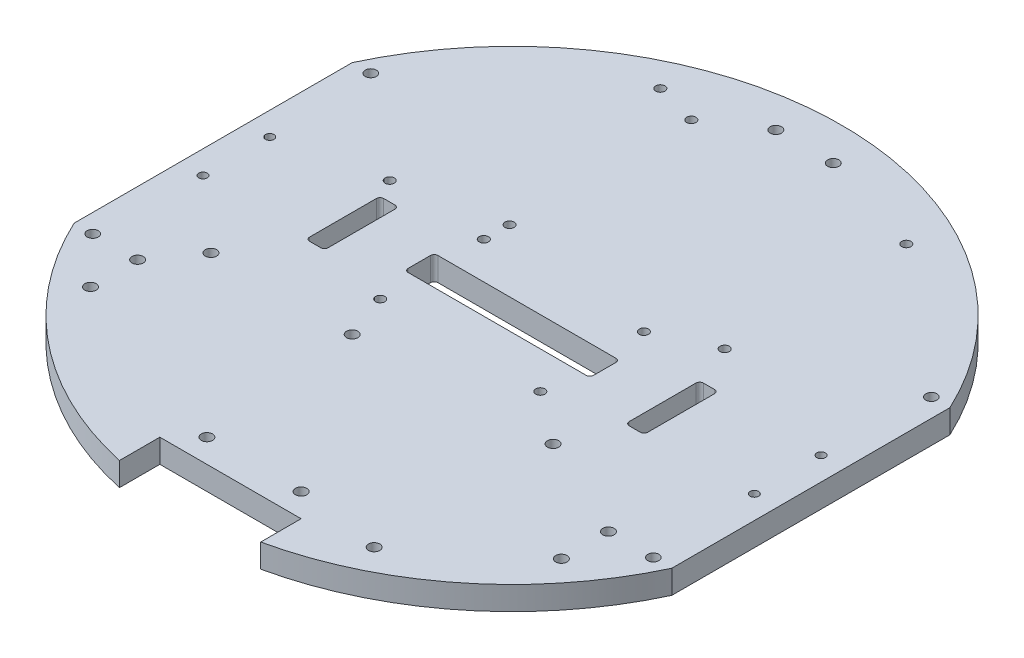
SolidWorks part; units mm, degrees
ref_plane "Front Plane" through (0, 0, 0) normal (0, 0, 1) x (1, 0, 0)
ref_plane "Top Plane" through (0, 0, 0) normal (0, 1, 0) x (1, 0, 0)
ref_plane "Right Plane" through (0, 0, 0) normal (1, 0, 0) x (0, 0, -1)
sketch "Sketch1" plane through (0, 0, 0) normal (0, 1, 0) x (1, 0, 0)
  line L0 (-80.6037, 37.5) -> (-80.6037, -37.5)
  line L1 (0, -88.9) -> (0, 88.9) construction
  line L2 (80.6037, 37.5) -> (80.6037, -37.5)
  arc A0 (-80.6037, -37.5) -> (80.6037, -37.5) centre (0, 0) ccw
  arc A1 (80.6037, 37.5) -> (-80.6037, 37.5) centre (0, 0) ccw
  dimension "D1" = 177.8
  dimension "D2" = 75
extrude "Main Body" add sketch "Sketch1" along normal blind 6.35
sketch "Sketch2" plane through (0, 6.35, 0) normal (0, 1, 0) x (1, 0, 0)
  line L0 (0, 88.9) -> (0, -88.9) construction
  line L1 (36.5, 69.85) -> (-21.5, 69.85) construction
  line L2 (36.5, 69.85) -> (36.5, 20.85) construction
  line L3 (36.5, 20.85) -> (-21.5, 20.85) construction
  line L4 (-21.5, 69.85) -> (-21.5, 20.85) construction
  line L5 (36.5, 69.85) -> (-21.5, 20.85) construction
  line L6 (36.5, 20.85) -> (-21.5, 69.85) construction
  circle A0 centre (36.5, 69.85) radius 1.25
  circle A1 centre (36.5, 20.85) radius 1.25
  circle A2 centre (-21.5, 20.85) radius 1.25
  circle A3 centre (-21.5, 69.85) radius 1.25
  arc A4 (-80.6037, -37.5) -> (80.6037, -37.5) centre (0, 0) ccw construction
  arc A5 (80.6037, 37.5) -> (-80.6037, 37.5) centre (0, 0) ccw construction
  point P0 (7.5, 45.35)
  point P11 (0, 88.9)
  dimension "D3" = 2.5
  dimension "D1" = 58
  dimension "D2" = 49
  dimension "D4" = 19.05
  dimension "D5" = 15
extrude "Raspberry Pi" cut sketch "Sketch2" against normal up to next
sketch "Sketch3" plane through (0, 6.35, 0) normal (0, 1, 0) x (1, 0, 0)
  line L0 (-80.6037, 0) -> (80.6037, 0) construction
  line L1 (-80.6037, 37.5) -> (-80.6037, -37.5) construction
  line L2 (80.6037, -37.5) -> (80.6037, 37.5) construction
  line L3 (-74.3537, -9) -> (-74.3537, 9) construction
  line L4 (0, -88.9) -> (0, 88.9) construction
  line L5 (74.3537, -9) -> (74.3537, 9) construction
  circle A0 centre (-74.3537, 9) radius 1.143
  circle A1 centre (-74.3537, -9) radius 1.143
  arc A2 (-80.6037, -37.5) -> (80.6037, -37.5) centre (0, 0) ccw construction
  arc A3 (80.6037, 37.5) -> (-80.6037, 37.5) centre (0, 0) ccw construction
  circle A4 centre (74.3537, 9) radius 1.143
  circle A5 centre (74.3537, -9) radius 1.143
  point P10 (-74.3537, 0)
  point P19 (74.3537, 0)
  dimension "D1" = 6.25
  dimension "D2" = 2.286
  dimension "D3" = 18
extrude "Motor Mounts" cut sketch "Sketch3" against normal up to next
sketch "Sketch4" plane through (0, 6.35, 0) normal (0, 1, 0) x (1, 0, 0)
  line L0 (0, -88.9) -> (0, 88.9) construction
  line L1 (-7.747, 78.9) -> (7.747, 78.9) construction
  arc A0 (-80.6037, -37.5) -> (80.6037, -37.5) centre (0, 0) ccw construction
  arc A1 (80.6037, 37.5) -> (-80.6037, 37.5) centre (0, 0) ccw construction
  circle A2 centre (-7.747, 78.9) radius 1.524
  circle A3 centre (7.747, 78.9) radius 1.524
  point P10 (0, 78.9)
  dimension "D1" = 3.048
  dimension "D2" = 15.494
  dimension "D3" = 10
extrude "Caster" cut sketch "Sketch4" against normal up to next
sketch "Sketch5" plane through (0, 6.35, 0) normal (0, 1, 0) x (1, 0, 0)
  line L0 (0, -88.9) -> (0, 88.9) construction
  line L1 (29.21, -82.5485) -> (29.21, 0.1133) construction
  line L2 (29.21, -24.4861) -> (50029.21, -24.4861) construction
  line L3 (29.21, -28.2961) -> (56.134, -28.2961) construction
  line L4 (29.21, -28.2961) -> (29.21, -68.9361) construction
  line L5 (29.21, -68.9361) -> (56.134, -68.9361) construction
  line L6 (56.134, -28.2961) -> (56.134, -68.9361) construction
  line L7 (29.21, -72.7461) -> (50029.21, -72.7461) construction
  line L8 (29.21, -28.2961) -> (29.21, -24.4861) construction
  line L9 (29.21, -68.9361) -> (29.21, -72.7461) construction
  line L10 (35.56, -24.4861) -> (35.56, -72.7461) construction
  arc A0 (-80.6037, -37.5) -> (80.6037, -37.5) centre (0, 0) ccw construction
  arc A1 (80.6037, 37.5) -> (-80.6037, 37.5) centre (0, 0) ccw construction
  circle A2 centre (35.56, -24.4861) radius 1.524
  circle A3 centre (35.56, -72.7461) radius 1.524
  dimension "D4" = 3.048
  dimension "D1" = 29.21
  dimension "D2" = 40.64
  dimension "D3" = 26.924
  dimension "D5" = 6.35
  dimension "D6" = 48.26
extrude "Grabber Mount" cut sketch "Sketch5" against normal through all
sketch "Sketch6" plane through (0, 6.35, 0) normal (0, 1, 0) x (1, 0, 0)
  line L0 (0, -88.1692) -> (0, -5.66) construction
  line L2 (-26.543, -75.692) -> (26.543, -75.692) construction
  line L3 (-26.543, -75.692) -> (-26.543, -63.5) construction
  line L4 (-26.543, -63.5) -> (26.543, -63.5) construction
  line L5 (26.543, -75.692) -> (26.543, -63.5) construction
  line L6 (-26.543, -75.692) -> (26.543, -63.5) construction
  line L7 (-26.543, -63.5) -> (26.543, -75.692) construction
  circle A0 centre (-12.7, -69.596) radius 1.524
  circle A1 centre (12.7, -69.596) radius 1.524
  point P1 (0, -69.596)
  dimension "D4" = 3.048
  dimension "D1" = 63.5
  dimension "D2" = 12.192
  dimension "D3" = 53.086
  dimension "D5" = 25.4
  dimension "D6" = 12.7
extrude "Front IR" cut sketch "Sketch6" against normal through all
sketch "Sketch8" plane through (0, 6.35, 0) normal (0, 1, 0) x (1, 0, 0)
  line L0 (0, 0) -> (0, 88.9) construction
  line L1 (-80.6037, 37.5) -> (-80.6037, -37.5) construction
  line L2 (-80.6037, -29.88) -> (80.6037, -29.88) construction
  line L3 (80.6037, -37.5) -> (80.6037, 37.5) construction
  line L4 (-80.6037, 23.206) -> (80.6037, 23.206) construction
  line L5 (0, 23.206) -> (0, -29.88) construction
  line L6 (0, -29.88) -> (0, -3.337) construction
  line L7 (-63.5, -37.5) -> (63.5, -37.5) construction
  circle A1 centre (-63.5, -37.5) radius 1.524
  circle A2 centre (-63.5, -50.2) radius 1.524
  circle A3 centre (63.5, -50.2) radius 1.524
  circle A4 centre (63.5, -37.5) radius 1.524
  dimension "D3" = 3.048
  dimension "D1" = 53.086
  dimension "D2" = 7.62
  dimension "D4" = 12.7
  dimension "D5" = 63.5
  dimension "D6" = 7.62
extrude "Side IR" cut sketch "Sketch8" against normal through all
sketch "Sketch9" plane through (0, 6.35, 0) normal (0, 1, 0) x (1, 0, 0)
  line L0 (35.56, -26.0101) -> (-80.6037, -26.0101) construction
  line L1 (-80.6037, 37.5) -> (-80.6037, -37.5) construction
  circle A0 centre (35.56, -24.4861) radius 1.524 construction
  circle A1 centre (-55.2037, -26.0101) radius 1.524
  circle A2 centre (-17.1037, -26.0101) radius 1.524
  dimension "D1" = 3.048
  dimension "D2" = 38.1
  dimension "D3" = 25.4
extrude "Pixy Mount" cut sketch "Sketch9" against normal through all
sketch "Sketch10" plane through (0, 6.35, 0) normal (0, 1, 0) x (1, 0, 0)
  line L0 (0, -88.9) -> (0, 0) construction
  line L1 (19.05, -101.854) -> (19.05, -75.946)
  line L2 (19.05, -101.854) -> (-19.05, -101.854)
  line L3 (19.05, -75.946) -> (-19.05, -75.946)
  line L4 (-19.05, -101.854) -> (-19.05, -75.946)
  line L5 (19.05, -101.854) -> (-19.05, -75.946) construction
  line L6 (19.05, -75.946) -> (-19.05, -101.854) construction
  arc A0 (-80.6037, -37.5) -> (80.6037, -37.5) centre (0, 0) ccw construction
  circle A1 centre (-12.7, -69.596) radius 1.524 construction
  dimension "D2" = 6.35
  dimension "D1" = 38.1
extrude "Grabber slot" cut sketch "Sketch10" against normal through all
sketch "Sketch11" plane through (0, 6.35, 0) normal (0, 1, 0) x (1, 0, 0)
  line L0 (0, 88.9) -> (0, -75.946) construction
  line L1 (19.05, -75.946) -> (-19.05, -75.946) construction
  line L2 (80.6037, 0) -> (-80.6037, 0) construction
  line L3 (80.6037, -37.5) -> (80.6037, 37.5) construction
  line L4 (-80.6037, 37.5) -> (-80.6037, -37.5) construction
  line L5 (-45.6037, 10) -> (-40.6037, 10)
  line L6 (25, -4) -> (-25, -4)
  line L7 (25, -4) -> (25, 4)
  line L8 (25, 4) -> (-25, 4)
  line L9 (-25, -4) -> (-25, 4)
  line L10 (25, -4) -> (-25, 4) construction
  line L11 (25, 4) -> (-25, -4) construction
  line L12 (45.6037, -10) -> (40.6037, -10)
  line L13 (45.6037, -10) -> (45.6037, 10)
  line L14 (45.6037, 10) -> (40.6037, 10)
  line L15 (40.6037, -10) -> (40.6037, 10)
  line L16 (45.6037, -10) -> (40.6037, 10) construction
  line L17 (45.6037, 10) -> (40.6037, -10) construction
  line L18 (-40.6037, -10) -> (-40.6037, 10)
  line L19 (-45.6037, -10) -> (-40.6037, -10)
  line L20 (-45.6037, -10) -> (-45.6037, 10)
  arc A0 (80.6037, 37.5) -> (-80.6037, 37.5) centre (0, 0) ccw construction
  point P13 (0, 0)
  point P19 (43.1037, 0)
  dimension "D3" = 35
  dimension "D1" = 8
  dimension "D2" = 50
  dimension "D4" = 20
  dimension "D5" = 5
extrude "Wire slots" cut sketch "Sketch11" against normal through all
sketch "Sketch13" plane through (0, 6.35, 0) normal (0, 1, 0) x (1, 0, 0)
  line L0 (0, 88.9) -> (0, -75.946) construction
  line L1 (19.05, -75.946) -> (-19.05, -75.946) construction
  line L2 (80.6037, 0) -> (-80.6037, 0) construction
  line L3 (80.6037, -37.5) -> (80.6037, 37.5) construction
  line L4 (-80.6037, 37.5) -> (-80.6037, -37.5) construction
  line L5 (80.6037, -37.5) -> (-80.6037, -37.5) construction
  line L6 (80.6037, 37.5) -> (-80.6037, 37.5) construction
  line L8 (75.6037, 37.5) -> (-75.6037, 37.5) construction
  line L9 (75.6037, 37.5) -> (75.6037, -37.5) construction
  line L10 (75.6037, -37.5) -> (-75.6037, -37.5) construction
  line L11 (-75.6037, 37.5) -> (-75.6037, -37.5) construction
  line L12 (75.6037, 37.5) -> (-75.6037, -37.5) construction
  line L13 (75.6037, -37.5) -> (-75.6037, 37.5) construction
  arc A0 (80.6037, 37.5) -> (-80.6037, 37.5) centre (0, 0) ccw construction
  circle A1 centre (75.6037, -37.5) radius 1.5
  circle A2 centre (-75.6037, -37.5) radius 1.5
  circle A3 centre (75.6037, 37.5) radius 1.5
  circle A4 centre (-75.6037, 37.5) radius 1.5
  point P21 (0, 0)
  dimension "D2" = 3
  dimension "D1" = 5
extrude "2nd level standoffs" cut sketch "Sketch13" against normal through all
fillet "Fillet1" radius 1 12 edges at (40.6037, 3.175, -10) (40.6037, 3.175, 10) (45.6037, 3.175, 10) (45.6037, 3.175, -10) (-45.6037, 3.175, 10) (-40.6037, 3.175, 10) (-45.6037, 3.175, -10) (-40.6037, 3.175, -10) (-25, 3.175, 4) (-25, 3.175, -4) (25, 3.175, 4) (25, 3.175, -4)
sketch "Sketch14" plane through (0, 6.35, 0) normal (0, 1, 0) x (1, 0, 0)
  line L1 (-21.59, -13.97) -> (21.59, -13.97) construction
  line L2 (-21.59, -13.97) -> (-21.59, 13.97) construction
  line L3 (-21.59, 13.97) -> (21.59, 13.97) construction
  line L4 (21.59, -13.97) -> (21.59, 13.97) construction
  line L5 (-21.59, -13.97) -> (21.59, 13.97) construction
  line L6 (-21.59, 13.97) -> (21.59, -13.97) construction
  circle A0 centre (-21.59, 13.97) radius 1.25
  circle A1 centre (21.59, 13.97) radius 1.25
  circle A2 centre (21.59, -13.97) radius 1.25
  circle A3 centre (-21.59, -13.97) radius 1.25
  point P0 (0, 0)
  dimension "D3" = 2.5
  dimension "D1" = 43.18
  dimension "D2" = 27.94
extrude "Encoder Perfboard" cut sketch "Sketch14" against normal blind 10
sketch "Sketch15" plane through (0, 6.35, 0) normal (0, 1, 0) x (1, 0, 0)
  line L1 (-30, 76) -> (-51, 76) construction
  line L2 (-30, 76) -> (-30, 12) construction
  line L3 (-30, 12) -> (-51, 12) construction
  line L4 (-51, 76) -> (-51, 12) construction
  line L5 (-30, 76) -> (-51, 12) construction
  line L6 (-30, 12) -> (-51, 76) construction
  circle A0 centre (-48, 15) radius 1.25
  circle A1 centre (-33, 73) radius 1.25
  point P0 (-40.5, 44)
  dimension "D6" = 3
  dimension "D7" = 2.5
  dimension "D9" = 3
  dimension "D10" = 2.5
  dimension "D1" = 21
  dimension "D2" = 64
  dimension "D3" = 12
  dimension "D4" = 30
  dimension "D5" = 3
  dimension "D8" = 3
extrude "Cut-Extrude2" cut sketch "Sketch15" against normal blind 10
